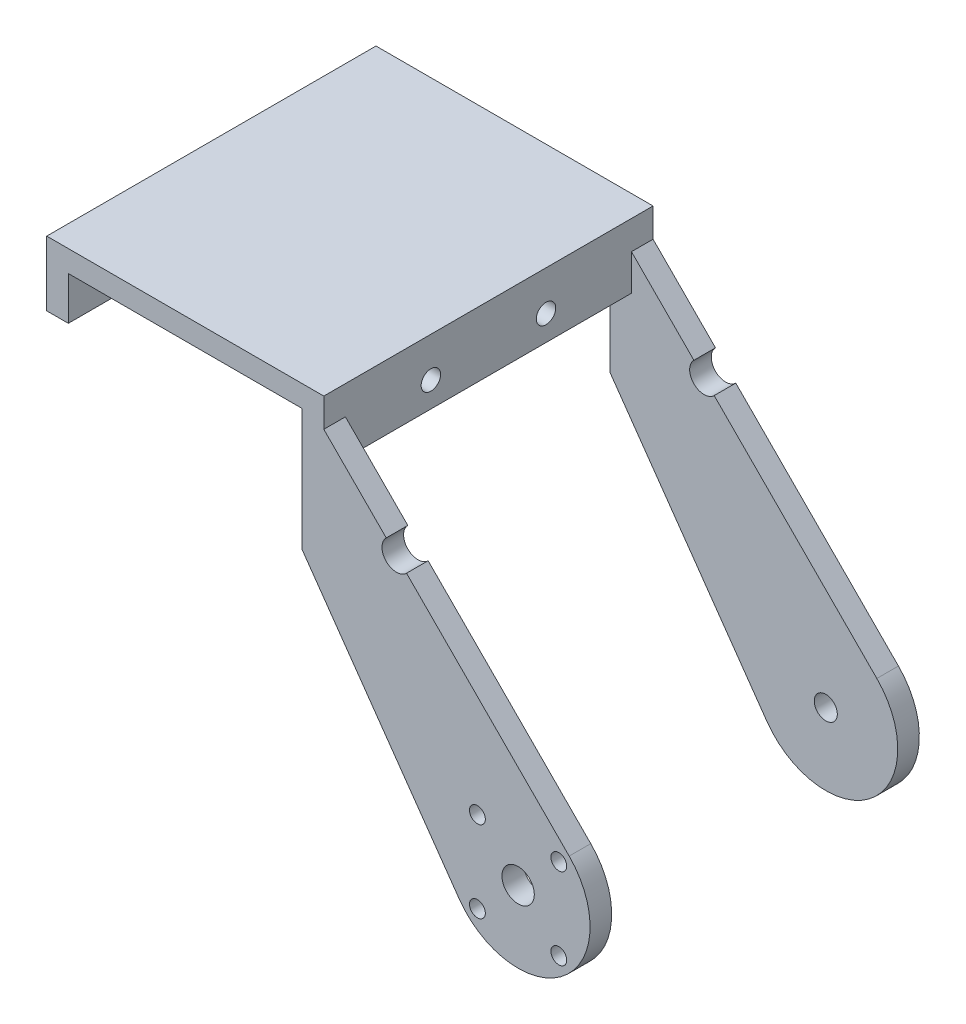
SolidWorks part; units mm, degrees
note: The reader was unsure of these and kept them because the rebuilt part matched: shared geometry of "Sketch1<3>", "Sketch1<4>", "Sketch1<5>".
ref_plane "Front Plane" through (0, 0, 0) normal (0, 0, 1) x (1, 0, 0)
ref_plane "Top Plane" through (0, 0, 0) normal (0, 1, 0) x (1, 0, 0)
ref_plane "Right Plane" through (0, 0, 0) normal (1, 0, 0) x (0, 0, -1)
sketch "Sketch1" plane through (0, 0, 0) normal (0, 1, 0) x (1, 0, 0)
  line L0 (-16.25, 22.875) -> (-16.25, -22.875)
  line L1 (19.25, 22.875) -> (-19.25, 22.875)
  line L2 (19.25, 22.875) -> (19.25, -22.875)
  line L3 (19.25, -22.875) -> (-19.25, -22.875)
  line L4 (-19.25, 22.875) -> (-19.25, -22.875)
  line L5 (19.25, 22.875) -> (-19.25, -22.875) construction
  line L6 (19.25, -22.875) -> (-19.25, 22.875) construction
  line L7 (16.25, 22.875) -> (16.25, -22.875)
  line L10 (-28.798, 0) -> (28.798, 0) construction
  line L13 (19.25, 19.875) -> (16.25, 19.875)
  line L14 (19.25, -19.875) -> (16.25, -19.875)
  point P0 (0, 0)
  dimension "D1" = 45.75
  dimension "D2" = 38.5
  dimension "D3" = 3
  dimension "D4" = 3
  dimension "D7" = 3
extrude "Boss-Extrude1" add sketch "Sketch1" against normal blind 3 contours L7 L1 L0 L3
extrude "Boss-Extrude2" add sketch "Sketch1<3>" against normal blind 9 contours L1 L4 L3 L0 | L1 L7 L3 L2
sketch "Sketch1<3>" plane through (0, 0, 0) normal (0, 1, 0) x (1, 0, 0) same geometry as "Sketch1"
extrude "Boss-Extrude3" add sketch "Sketch1<4>" against normal blind 6
sketch "Sketch1<4>" plane through (0, 0, 0) normal (0, 1, 0) x (1, 0, 0) same geometry as "Sketch1"
sketch "Sketch3" plane through (-19.25, 0, 0) normal (-1, 0, 0) x (0, 0, 1)
  line L0 (-22.875, -9) -> (22.875, -9) construction
  circle A0 centre (-8, -5.5) radius 1.35
  dimension "D1" = 2.7
  dimension "D2" = 3.5
  dimension "D3" = 8
extrude "Cut-Extrude1" cut sketch "Sketch3" against normal up to surface (38.5 mm away) up to face at (19.25, -4.5, 0)
mirror "Mirror1" about plane through (0, 0, 0) normal (0, 0, 1) of "Cut-Extrude1"
ref_plane "Plane1" through (0, 0, 22.875) normal (0, 0, 1) x (1, 0, 0)
extrude "Boss-Extrude4" add sketch "Sketch1<5>" against normal blind 20 contours L13 L2 L1 L7 | L2 L14 L7 L3
sketch "Sketch1<5>" plane through (0, 0, 0) normal (0, 1, 0) x (1, 0, 0) same geometry as "Sketch1"
sketch "Sketch4" plane through (0, 0, 22.875) normal (0, 0, 1) x (1, 0, 0)
  line L0 (19.25, -45.36) -> (46.25, -45.36) construction
  line L1 (19.25, -4) -> (19.25, -45.36) construction
  line L2 (19.25, -4) -> (46.25, -45.36) construction
  line L3 (19.25, -4) -> (53.3436, -38.3115)
  line L4 (16.25, -20) -> (38.0628, -51.1019)
  line L5 (19.25, -4) -> (16.25, -20)
  line L6 (19.25, -20) -> (19.25, 0) construction
  arc A0 (38.0628, -51.1019) -> (53.3436, -38.3115) centre (46.25, -45.36) ccw
  dimension "D3" = 20
  dimension "D1" = 27
  dimension "D2" = 41.36
  dimension "D4" = 5
extrude "Boss-Extrude5" add sketch "Sketch4" against normal blind 3
mirror "Mirror2" about plane through (0, 0, 0) normal (0, 0, 1) of "Boss-Extrude5"
sketch "Sketch5" plane through (0, 0, 22.875) normal (0, 0, 1) x (1, 0, 0)
  line L0 (46.25, -45.36) -> (51.9069, -39.7031) construction
  line L1 (19.25, -45.36) -> (46.25, -45.36) construction
  circle A0 centre (46.25, -45.36) radius 2.25
  circle A1 centre (51.9069, -39.7031) radius 1.1
  dimension "D1" = 4.5
  dimension "D4" = 2.2
  dimension "D2" = 135
  dimension "D3" = 8
extrude "Cut-Extrude2" cut sketch "Sketch5" against normal up to surface (3 mm away) up to face at (28.2286, -23.2892, 19.875)
sketch "Sketch6" plane through (0, 0, -22.875) normal (0, 0, -1) x (-1, 0, 0)
  circle A0 centre (-46.25, -45.36) radius 1.6
  dimension "D1" = 3.2
extrude "Cut-Extrude3" cut sketch "Sketch6" against normal up to surface (3 mm away) up to face at (28.2286, -23.2892, -19.875)
pattern_circular "CirPattern1" count 4 over 360 about axis through (46.25, -45.36, 0) along (0, 0, 1) of "Cut-Extrude2"
sketch "Sketch7" plane through (0, 0, 22.875) normal (0, 0, 1) x (1, 0, 0)
  line L0 (53.3436, -38.3115) -> (19.25, -4) construction
  line L1 (27.9249, -12.7304) -> (30.7443, -15.5678)
  arc A0 (27.9249, -12.7304) -> (30.7443, -15.5678) centre (29.3346, -14.1491) ccw
  circle A1 centre (46.25, -45.36) radius 2.25 construction
  dimension "D1" = 35.5
  dimension "D2" = 2
extrude "Cut-Extrude4" cut sketch "Sketch7" against normal up to surface (45.75 mm away) up to face at (44.65, -45.36, -22.875)
move or copy body "Body-Move/Copy1" [suppressed] bodies to move or copy 112
